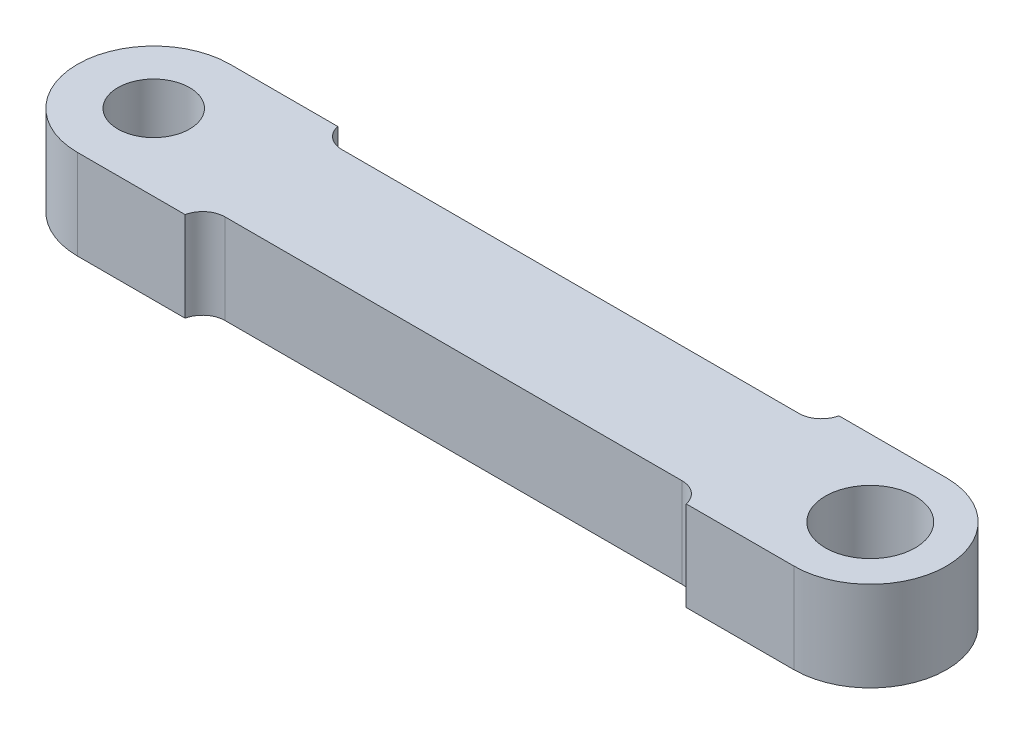
SolidWorks part; units mm, degrees
ref_plane "Front" through (0, 0, 0) normal (0, 0, 1) x (1, 0, 0)
ref_plane "Top" through (0, 0, 0) normal (0, 1, 0) x (1, 0, 0)
ref_plane "Right" through (0, 0, 0) normal (1, 0, 0) x (0, 0, -1)
sketch "Sketch1" plane through (0, 0, 0) normal (0, 1, 0) x (1, 0, 0)
  line L0 (120, 85) -> (120, 65)
  line L1 (678, 85) -> (678, 65)
  line L2 (0, 85) -> (120, 85)
  line L3 (0, -85) -> (120, -85)
  line L4 (678, 85) -> (798, 85)
  line L5 (678, -85) -> (798, -85)
  line L6 (678, -65) -> (678, -85)
  line L7 (120, -65) -> (678, -65)
  line L8 (120, 65) -> (678, 65)
  line L9 (120, -65) -> (120, -85)
  arc A0 (0, 85) -> (0, -85) centre (0, 0) ccw
  arc A1 (798, -85) -> (798, 85) centre (798, 0) ccw
  circle A2 centre (798, 0) radius 50
  circle A3 centre (0, 0) radius 40
  dimension "D1" = 170
  dimension "D2" = 170
  dimension "D3" = 798
  dimension "D4" = 120
  dimension "D5" = 120
extrude "Boss-Extrude1" add sketch "Sketch1" along normal blind 100
fillet "Fillet1" radius 25 4 edges at (120, 50, 65) (678, 50, 65) (678, 50, -65) (120, 50, -65)
